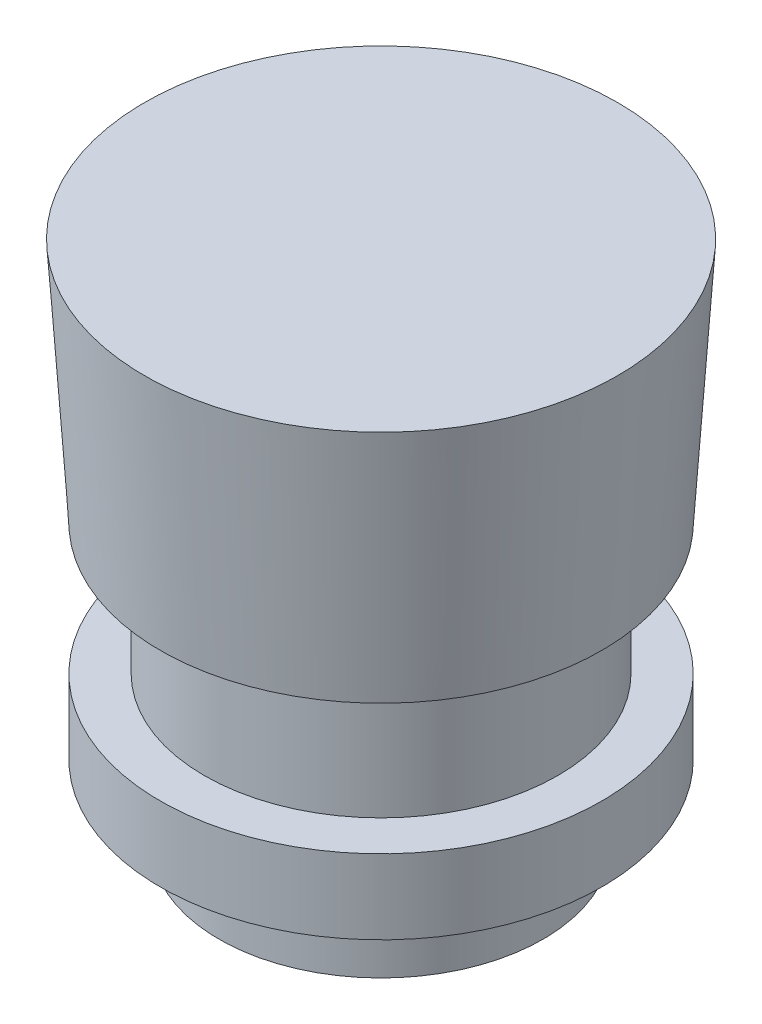
SolidWorks part; units mm, degrees
ref_plane "Front Plane" through (0, 0, 0) normal (0, 0, 1) x (1, 0, 0)
ref_plane "Top Plane" through (0, 0, 0) normal (0, 1, 0) x (1, 0, 0)
ref_plane "Right Plane" through (0, 0, 0) normal (1, 0, 0) x (0, 0, -1)
ref_axis "Axis1" through (0, 55, 0) along (0, -1, 0)
sketch "Sketch1" plane through (0, 0, 0) normal (0, 0, 1) x (1, 0, 0)
  line L0 (0, 0) -> (0, 17.907) construction
  line L1 (0, 17.907) -> (-16.129, 17.907)
  line L2 (-16.129, 17.907) -> (-15.049, 1.143)
  line L3 (-15.049, 1.143) -> (-12.049, 1.143)
  line L4 (-12.049, 1.143) -> (-12.049, -7.747)
  line L5 (-12.049, -7.747) -> (-15.049, -7.747)
  line L6 (-15.049, -7.747) -> (-15.049, -12.827)
  line L7 (-15.049, -12.827) -> (-11.049, -12.827)
  line L8 (-11.049, -12.827) -> (-11.049, -17.907)
  line L9 (-11.049, -17.907) -> (0, -17.907)
  line L10 (0, -17.907) -> (0, 0)
  line L11 (0, 0) -> (0, 17.907)
  dimension "D1" = 16.764
  dimension "D2" = 25.654
  dimension "D3" = 35.814
  dimension "D4" = 16.129
  dimension "D5" = 11.049
  dimension "D6" = 3
  dimension "D7" = 4
revolve "Revolve1" add sketch "Sketch1" angle 360 about L0
